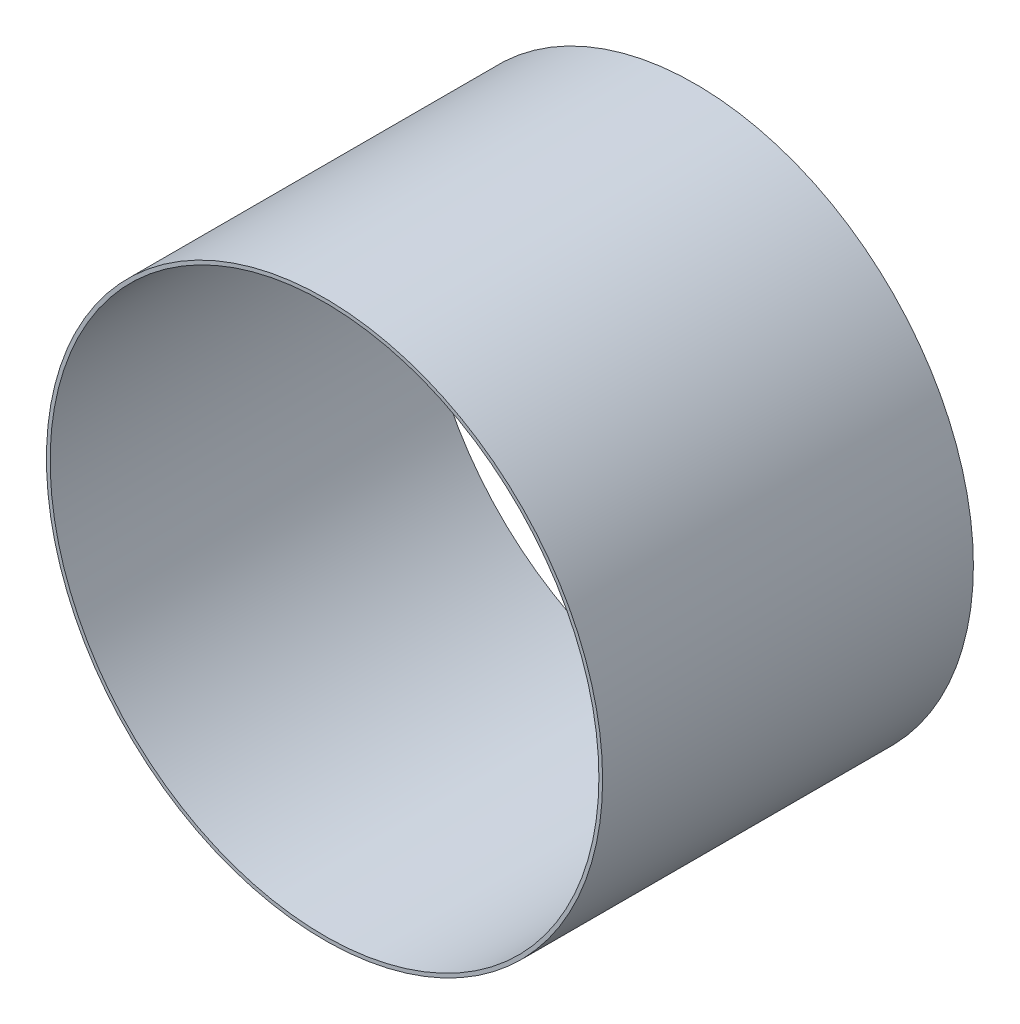
SolidWorks part; units mm, degrees
ref_plane "前视基准面" through (0, 0, 0) normal (0, 0, 1) x (1, 0, 0)
ref_plane "上视基准面" through (0, 0, 0) normal (0, 1, 0) x (1, 0, 0)
ref_plane "右视基准面" through (0, 0, 0) normal (1, 0, 0) x (0, 0, -1)
sketch "草图1" plane through (0, 0, 0) normal (0, 0, 1) x (1, 0, 0)
  circle A0 centre (0, 0) radius 75
  dimension "D1" = 150
extrude "凸台-拉伸1" add sketch "草图1" along normal blind 100
shell "抽壳1" thickness 1 removed face at (75, 0, 0) removed face at (75, 0, 100)
